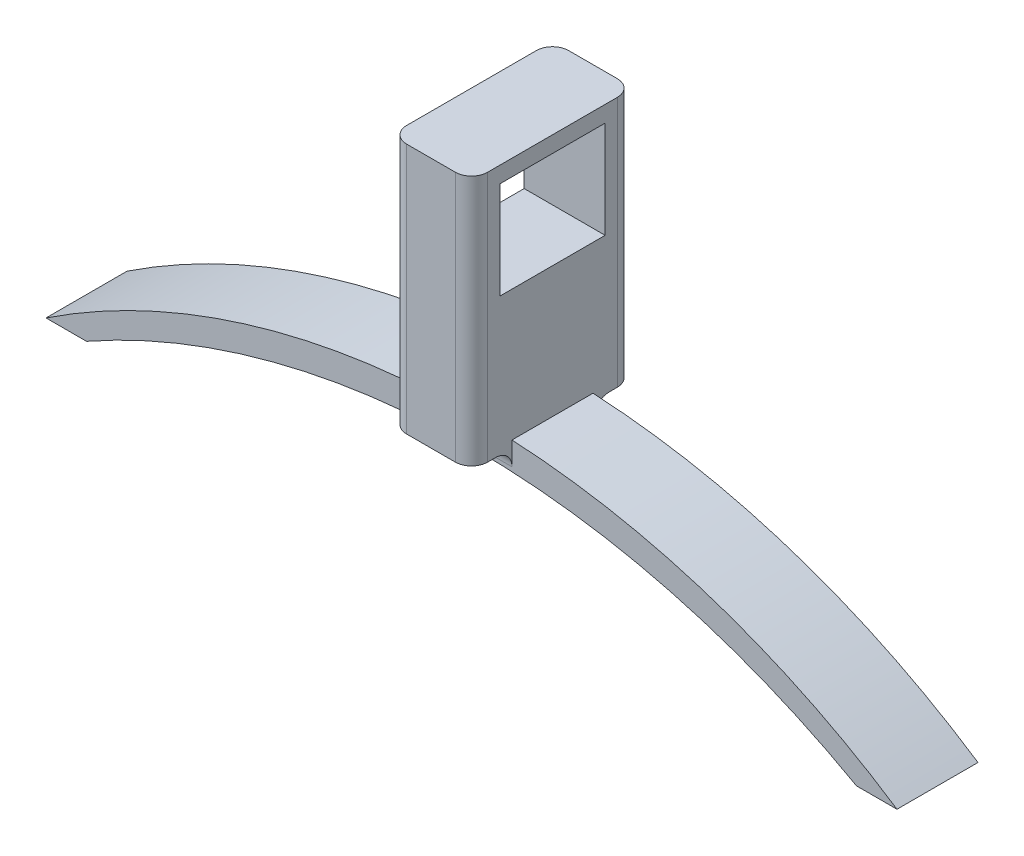
SolidWorks part; units mm, degrees
ref_plane "Front Plane" through (0, 0, 0) normal (0, 0, 1) x (1, 0, 0)
ref_plane "Top Plane" through (0, 0, 0) normal (0, 1, 0) x (1, 0, 0)
ref_plane "Right Plane" through (0, 0, 0) normal (1, 0, 0) x (0, 0, -1)
sketch "Sketch1" plane through (0, 0, 0) normal (0, 0, 1) x (1, 0, 0)
  line L0 (0, 0) -> (5, 0)
  line L1 (105.0571, 0) -> (100.0571, 0)
  arc A0 (0, 0) -> (105.0571, 0) centre (52.5286, -79.1312) cw
  arc A1 (5, 0) -> (100.0571, 0) centre (52.5286, -84.4689) cw
extrude "Boss-Extrude1" add sketch "Sketch1" along normal blind 10
scale "Scale1" scale about centroid uniform scaling yes scale factor 0.5
ref_plane "Plane5" through (0, 12.7861, 0) normal (0, 1, 0) x (1, 0, 0)
sketch "Sketch4" plane through (0, 12.7861, 0) normal (0, 1, 0) x (1, 0, 0)
  line L0 (26.2643, -7.5) -> (78.7928, -7.5) construction
  line L1 (26.2643, -7.5) -> (78.7928, -7.5)
  line L2 (78.7928, -2.5) -> (26.2643, -2.5) construction
  line L3 (78.7928, -2.5) -> (26.2643, -2.5)
  line L4 (52.5286, -2.5) -> (52.5286, -7.5)
  line L6 (50.0286, 0) -> (55.0286, 0)
  line L7 (50.0286, 0) -> (50.0286, -10)
  line L8 (50.0286, -10) -> (55.0286, -10)
  line L9 (55.0286, 0) -> (55.0286, -10)
  line L10 (50.0286, 0) -> (55.0286, -10) construction
  line L11 (50.0286, -10) -> (55.0286, 0) construction
  point P6 (52.5286, -5)
  dimension "D1" = 10
  dimension "D2" = 5
extrude "Boss-Extrude4" add sketch "Sketch4" along normal blind 15 separate body contours L9 L3 L4 L1 | L9 L6 L7 L3 | L3 L7 L1 L4 | L9 L1 L7 L8 region at (51.2786, 12.7861, 5) region at (52.5286, 12.7861, 8.75) region at (53.7786, 12.7861, 5) region at (52.5286, 12.7861, 1.25)
sketch "Sketch5" plane through (0, 12.7861, 0) normal (0, -1, 0) x (1, 0, 0)
  line L4 (50.0286, 0) -> (55.0286, 0)
  line L5 (55.0286, 0) -> (55.0286, 10)
  line L6 (55.0286, 10) -> (50.0286, 10)
  line L7 (50.0286, 10) -> (50.0286, 0)
  line L8 (50.0286, 0) -> (55.0286, 0)
  line L9 (55.0286, 0) -> (55.0286, 10)
  line L10 (55.0286, 10) -> (50.0286, 10)
  line L11 (50.0286, 10) -> (50.0286, 0)
  dimension "D1" = 0
extrude "Boss-Extrude5" add sketch "Sketch5" along normal blind 0.5
fillet "Fillet1" radius 1 6 edges at (52.5286, 12.2861, 2.5) (52.5286, 12.2861, 7.5) (50.0286, 20.0361, 0) (55.0286, 20.0361, 0) (55.0286, 20.0361, 10) (50.0286, 20.0361, 10)
sketch "Sketch6" plane through (55.0286, 0, 0) normal (1, 0, 0) x (0, 0, -1)
  line L0 (-1, 27.7861) -> (-9, 27.7861) construction
  line L1 (-1, 27.7861) -> (-9, 27.7861)
  line L2 (-5, 27.7861) -> (-5, 13.1201) construction
  line L4 (-1.75, 26.7861) -> (-8.25, 26.7861)
  line L5 (-1.75, 26.7861) -> (-1.75, 20.7861)
  line L6 (-1.75, 20.7861) -> (-8.25, 20.7861)
  line L7 (-8.25, 26.7861) -> (-8.25, 20.7861)
  line L8 (-1.75, 26.7861) -> (-8.25, 20.7861) construction
  line L9 (-1.75, 20.7861) -> (-8.25, 26.7861) construction
  point P4 (-5, 23.7861)
  dimension "D1" = 4
  dimension "D2" = 6
  dimension "D3" = 6.5
extrude "Cut-Extrude1" cut sketch "Sketch6" against normal through all contours L4 L7 L6 L5 region at (55.0286, 23.7861, 5)
